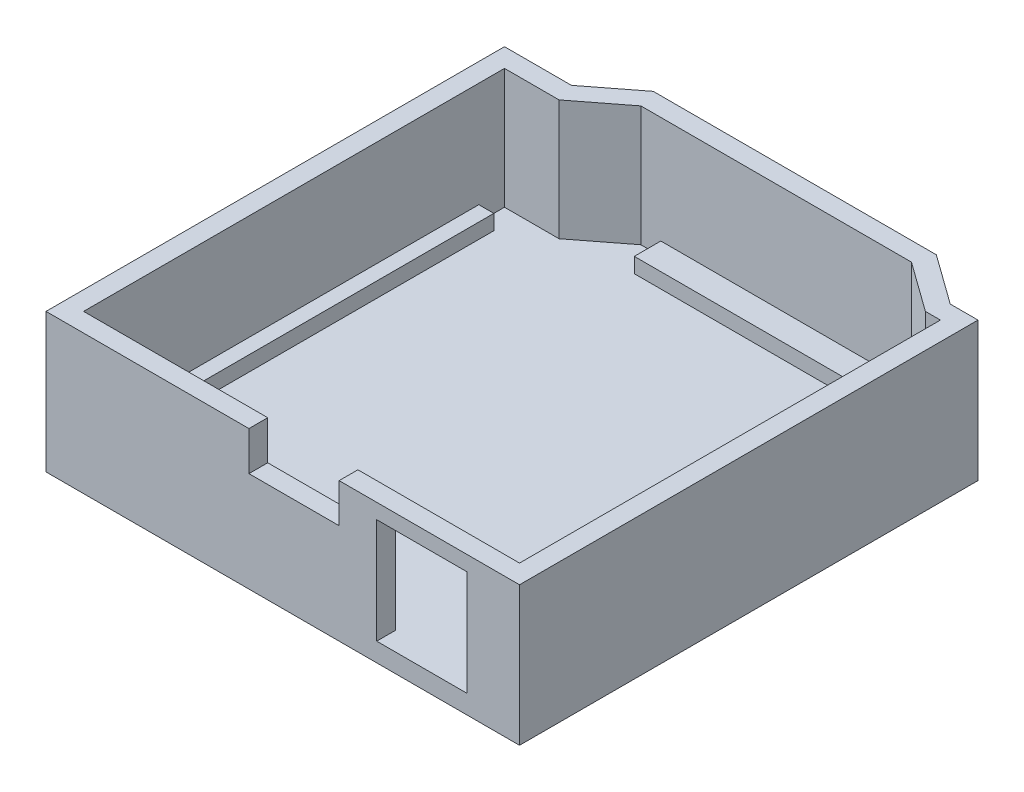
SolidWorks part; units mm, degrees
ref_plane "Front Plane" through (0, 0, 0) normal (0, 0, 1) x (1, 0, 0)
ref_plane "Top Plane" through (0, 0, 0) normal (0, 1, 0) x (1, 0, 0)
ref_plane "Right Plane" through (0, 0, 0) normal (1, 0, 0) x (0, 0, -1)
sketch "Sketch1" plane through (0, 0, 0) normal (0, 1, 0) x (1, 0, 0)
  line L0 (0, 0) -> (0, 56)
  line L1 (0, 56) -> (7.2606, 56)
  line L2 (7.2606, 56) -> (13.3994, 60.7502)
  line L3 (13.3994, 60.7502) -> (49.3994, 60.7502)
  line L4 (0, 0) -> (58, 0)
  line L5 (58, 0) -> (58, 56)
  line L7 (58, 56) -> (56, 56)
  line L8 (56, 56) -> (49.3994, 60.7502)
  dimension "D1" = 56
  dimension "D2" = 58
  dimension "D3" = 2
  dimension "D4" = 36
extrude "Boss-Extrude1" add sketch "Sketch1" along normal blind 16
shell "Shell1" thickness 2.5 removed face at (30.2574, 16, -43.1876) outward yes
sketch "Sketch2" plane through (0, 0, 0) normal (0, 0, -1) x (-1, 0, 0)
  line L5 (2.5, -2.5) -> (-60.5, -2.5) construction
  line L10 (-60.5, 16) -> (-60.5, -2.5) construction
  line L11 (-41.5, 14) -> (-53.5, 14)
  line L12 (-41.5, 14) -> (-41.5, 0)
  line L13 (-41.5, 0) -> (-53.5, 0)
  line L14 (-53.5, 14) -> (-53.5, 0)
  line L15 (2.5, 16) -> (-60.5, 16) construction
  line L16 (-24.5, 10.8048) -> (-36.5, 10.8048)
  line L17 (-24.5, 10.8048) -> (-24.5, 16)
  line L18 (-24.5, 16) -> (-36.5, 16)
  line L19 (-36.5, 10.8048) -> (-36.5, 16)
  dimension "D1" = 2.5
  dimension "D2" = 36
  dimension "D3" = 12
  dimension "D4" = 7
  dimension "D5" = 12
extrude "Cut-Extrude1" cut sketch "Sketch2" against normal blind 4
sketch "Sketch3" plane through (0, 0, 0) normal (0, 1, 0) x (1, 0, 0)
  line L0 (0, 56) -> (0, 0) construction
  line L1 (0, 52.5835) -> (2, 52.5835)
  line L2 (0, 52.5835) -> (0, 2.5835)
  line L3 (0, 2.5835) -> (2, 2.5835)
  line L4 (2, 52.5835) -> (2, 2.5835)
  line L7 (57.8762, 52.5835) -> (56.0617, 52.5835)
  line L8 (57.8762, 2.5835) -> (56.0617, 2.5835)
  line L9 (56.0617, 52.5835) -> (56.0617, 2.5835)
  line L10 (57.8762, 52.5835) -> (57.8762, 2.5835)
  dimension "D1" = 2
  dimension "D2" = 50
extrude "Boss-Extrude2" add sketch "Sketch3" along normal blind 2
sketch "Sketch4" plane through (0, 0, 0) normal (0, 1, 0) x (1, 0, 0)
  line L1 (16.2938, 60.5067) -> (47.3114, 60.5067)
  line L2 (16.2938, 60.5067) -> (16.2938, 56.9763)
  line L3 (16.2938, 56.9763) -> (47.3114, 56.9763)
  line L4 (47.3114, 60.5067) -> (47.3114, 56.9763)
extrude "Boss-Extrude3" add sketch "Sketch4" along normal blind 2
